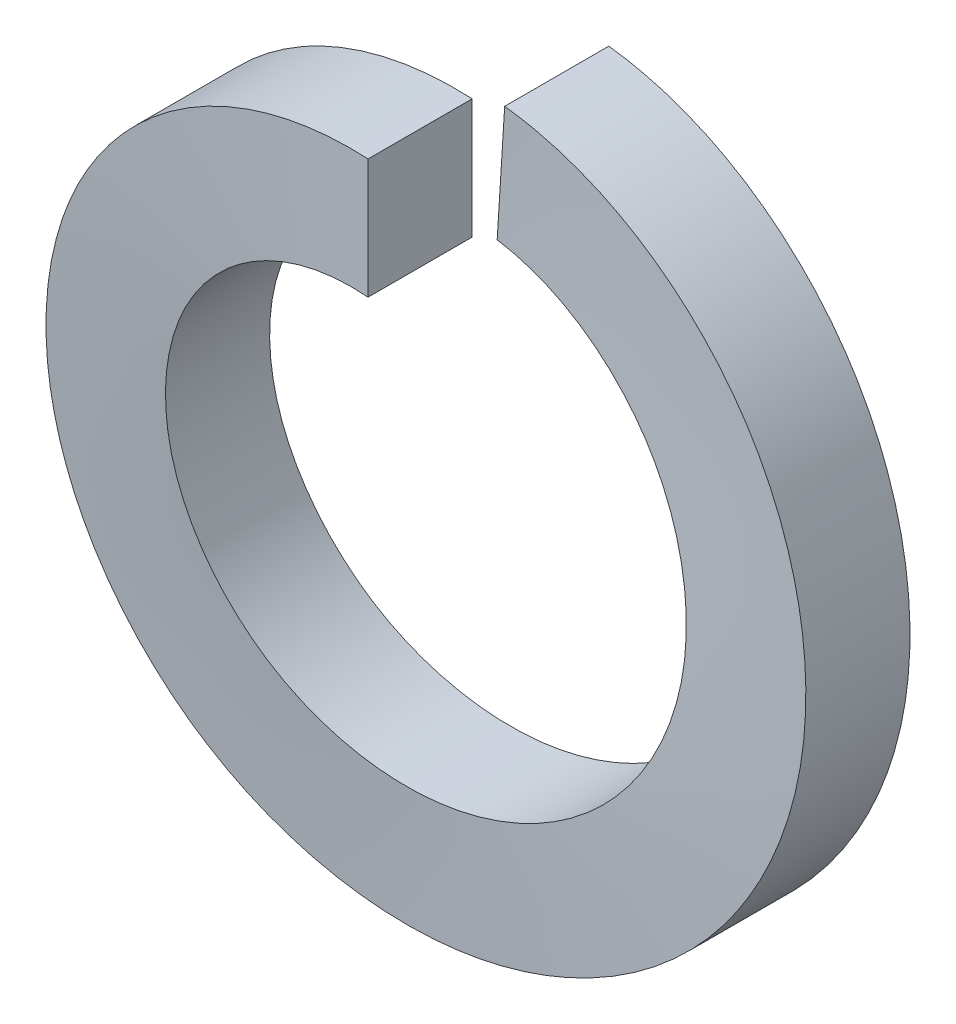
SolidWorks part; units mm, degrees
material "AISI 304"
ref_plane "Front Plane" through (0, 0, 0) normal (0, 0, 1) x (1, 0, 0)
ref_plane "Top Plane" through (0, 0, 0) normal (0, 1, 0) x (1, 0, 0)
ref_plane "Right Plane" through (0, 0, 0) normal (1, 0, 0) x (0, 0, -1)
sketch "Sketch1" plane through (0, 0, 0) normal (0, 0, 1) x (1, 0, 0)
  line L0 (0, 2.5654) -> (0, 1.6891) construction
  circle A0 centre (0, 0) radius 2.5654
  circle A1 centre (0, 0) radius 1.6891 construction
  dimension "ID" = 3.3782
  dimension "OD" = 5.1308
curve "Helix/Spiral1" pitch 0.8467 height 0.8382 radius 2.5654 left hand yes centre (0, 0, 0) axis (0, 0, -1) start towards (0, 1, 0) parameters "HT"=0.8382
sketch "Sketch2" plane through (0, 0, 0) normal (1, 0, 0) x (0, 0, -1)
  line L1 (0, 2.5654) -> (-0.762, 2.5654)
  line L2 (0, 2.5654) -> (0, 1.6891)
  line L3 (0, 1.6891) -> (-0.762, 1.6891)
  line L4 (-0.762, 2.5654) -> (-0.762, 1.6891)
  dimension "THK" = 0.762
sweep "Sweep1" add profiles "Sketch2" path "Helix/Spiral1"
equation "\"HT@Helix/Spiral1\" = \"THK@Sketch2\"*1.1"
